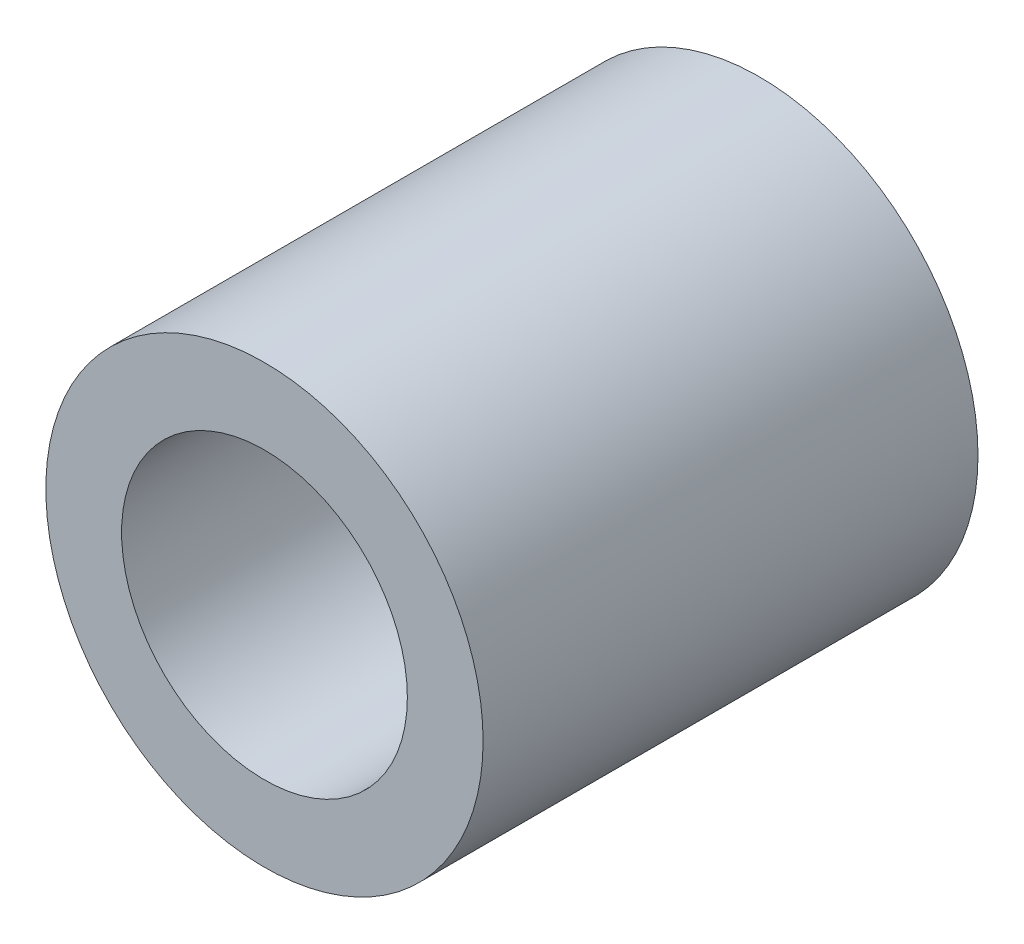
SolidWorks part; units mm, degrees
material "Silicon Rubber"
ref_plane "Front" through (0, 0, 0) normal (0, 0, 1) x (1, 0, 0)
ref_plane "Top" through (0, 0, 0) normal (0, 1, 0) x (1, 0, 0)
ref_plane "Right" through (0, 0, 0) normal (1, 0, 0) x (0, 0, -1)
ref_axis "Axis1" through (0, 0, 55) along (0, 0, -1)
sketch "Sketch1" plane through (0, 0, 0) normal (0, 0, 1) x (1, 0, 0)
  circle A0 centre (0, 0) radius 16.8314
  circle A1 centre (0, 0) radius 11
  dimension "D1" = 22
  dimension "D2" = 33.6628
extrude "Boss-Extrude1" add sketch "Sketch1" against normal blind 38.1
